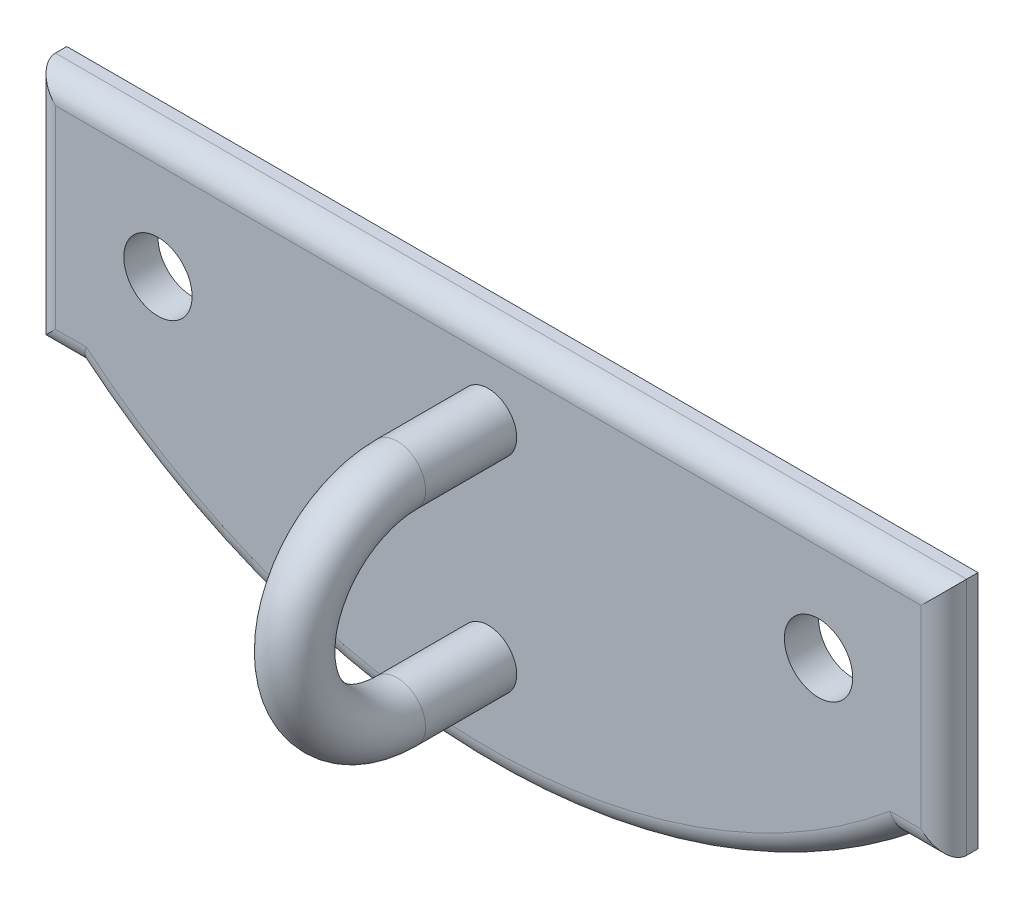
SolidWorks part; units mm, degrees
ref_plane "Front" through (0, 0, 0) normal (0, 0, 1) x (1, 0, 0)
ref_plane "Top" through (0, 0, 0) normal (0, 1, 0) x (1, 0, 0)
ref_plane "Right" through (0, 0, 0) normal (1, 0, 0) x (0, 0, -1)
sketch "Sketch1" plane through (0, 0, 0) normal (0, 0, 1) x (1, 0, 0)
  line L0 (0, 0) -> (20, 0)
  line L1 (55, 0) -> (-55, 0) construction
  line L2 (20, 0) -> (20, -10.5)
  line L3 (20, -10.5) -> (18, -10.5)
  line L4 (0, 0) -> (-20, 0)
  line L5 (-20, 0) -> (-20, -10.5)
  line L6 (-20, -10.5) -> (-18, -10.5)
  arc A1 (18, -10.5) -> (-18, -10.5) centre (0, 11.5706) cw
  dimension "D7" = 28.48
  dimension "D1" = 20
  dimension "D2" = 20
  dimension "D3" = 2
  dimension "D4" = 2
  dimension "D5" = 10.5
  dimension "D6" = 10.5
extrude "Boss-Extrude1" add sketch "Sketch1" along normal blind 1.5
sketch "Sketch2" plane through (0, 0, 1.5) normal (0, 0, 1) x (1, 0, 0)
  line L0 (-20, 0) -> (-20, -10.5) construction
  line L1 (0.825, 0) -> (-0.825, 0) construction
  line L2 (0, -0.825) -> (0, 0.825) construction
  circle A0 centre (-14.5, -5.25) radius 1.5
  circle A1 centre (14.5, -5.25) radius 1.5
  dimension "D1" = 5.5
  dimension "D3" = 3
  dimension "D2" = 5.25
extrude "Cut-Extrude1" cut sketch "Sketch2" against normal blind 1.5
sketch "Sketch3" plane through (0, 0, 1.5) normal (0, 0, 1) x (1, 0, 0)
  line L0 (0, -0.825) -> (0, 0.825) construction
  line L1 (0.825, 0) -> (-0.825, 0) construction
  circle A1 centre (0, -12.5) radius 1.25
  dimension "D2" = 2.5
  dimension "D4" = 12.5
sketch "Sketch4" plane through (0, 0, 0) normal (1, 0, 0) x (0, 0, -1)
  line L0 (-5.5, -3.5) -> (-1.5, -3.5)
  line L1 (-1.5, -12.5) -> (-5.5, -12.5)
  line L4 (-1.5, -3.75) -> (-1.5, -6.75) construction
  arc A0 (-5.5, -12.5) -> (-5.5, -3.5) centre (-5.5, -8) cw
  point P0 (0, 0)
  dimension "D1" = 4
  dimension "D2" = 9
sweep "Sweep2" add profiles "Sketch3" path "Sketch4"
fillet "Fillet1" radius 1 6 edges at (0, 0, 1.5) (20, -5.25, 1.5) (19, -10.5, 1.5) (0, -16.9094, 1.5) (-19, -10.5, 1.5) (-20, -5.25, 1.5)
